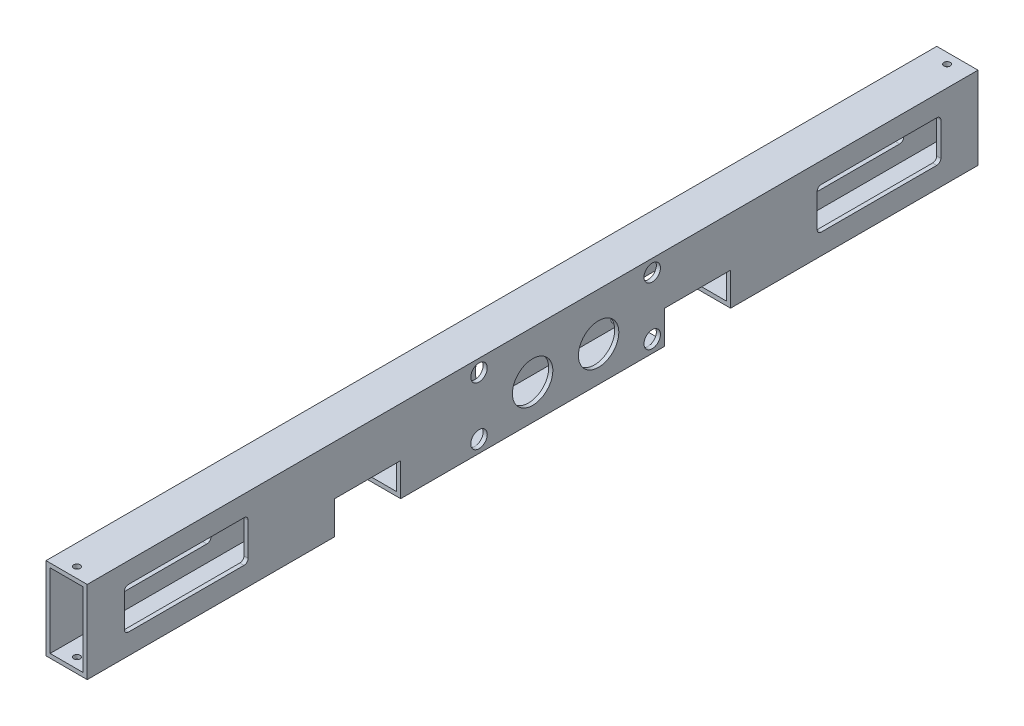
SolidWorks part; units mm, degrees
ref_plane "Front Plane" through (0, 0, 0) normal (0, 0, 1) x (1, 0, 0)
ref_plane "Top Plane" through (0, 0, 0) normal (0, 1, 0) x (1, 0, 0)
ref_plane "Right Plane" through (0, 0, 0) normal (1, 0, 0) x (0, 0, -1)
sketch "Sketch1" plane through (0, 0, 0) normal (0, 0, 1) x (1, 0, 0)
  line L1 (-12.1647, 2.5103) -> (19.5853, 2.5103)
  line L2 (-12.1647, 2.5103) -> (-12.1647, -60.9897)
  line L3 (-12.1647, -60.9897) -> (19.5853, -60.9897)
  line L4 (19.5853, 2.5103) -> (19.5853, -60.9897)
  line L5 (-8.9897, -0.6647) -> (16.4103, -0.6647)
  line L6 (-8.9897, -0.6647) -> (-8.9897, -57.8147)
  line L7 (-8.9897, -57.8147) -> (16.4103, -57.8147)
  line L8 (16.4103, -0.6647) -> (16.4103, -57.8147)
  dimension "D1" = 63.5
  dimension "D2" = 31.75
  dimension "D3" = 3.175
  dimension "D4" = 3.175
  dimension "D5" = 3.175
  dimension "D6" = 3.175
extrude "Boss-Extrude1" add sketch "Sketch1" along normal blind 685.8
sketch "Sketch3" plane through (-12.1647, 0, 0) normal (-1, 0, 0) x (0, 0, 1)
  line L0 (0, 2.5103) -> (0, -60.9897) construction
  line L1 (31.7754, -13.3647) -> (120.6754, -13.3647)
  line L2 (28.6004, -16.5397) -> (28.6004, -41.9397)
  line L3 (31.7754, -45.1147) -> (120.6754, -45.1147)
  line L4 (123.8504, -16.5397) -> (123.8504, -41.9397)
  line L5 (685.8, 2.5103) -> (0, 2.5103) construction
  line L6 (685.8, -60.9897) -> (0, -60.9897) construction
  line L7 (342.9, 2.5103) -> (342.9, -60.9897)
  line L8 (561.9496, -16.5397) -> (561.9496, -41.9397)
  line L9 (654.0246, -45.1147) -> (565.1246, -45.1147)
  line L10 (657.1996, -16.5397) -> (657.1996, -41.9397)
  line L11 (654.0246, -13.3647) -> (565.1246, -13.3647)
  line L12 (685.8, 2.5103) -> (685.8, -60.9897) construction
  line L13 (190.5, -60.9897) -> (241.3, -60.9897)
  line L14 (190.5, -60.9897) -> (190.5, -35.5897)
  line L15 (190.5, -35.5897) -> (241.3, -35.5897)
  line L16 (241.3, -60.9897) -> (241.3, -35.5897)
  line L17 (444.5, -60.9897) -> (495.3, -60.9897)
  line L18 (495.3, -60.9897) -> (495.3, -35.5897)
  line L19 (495.3, -35.5897) -> (444.5, -35.5897)
  line L20 (444.5, -60.9897) -> (444.5, -35.5897)
  arc A0 (28.6004, -41.9397) -> (31.7754, -45.1147) centre (31.7754, -41.9397) ccw
  arc A1 (120.6754, -45.1147) -> (123.8504, -41.9397) centre (120.6754, -41.9397) ccw
  arc A2 (120.6754, -13.3647) -> (123.8504, -16.5397) centre (120.6754, -16.5397) cw
  arc A3 (31.7754, -13.3647) -> (28.6004, -16.5397) centre (31.7754, -16.5397) ccw
  arc A4 (654.0246, -13.3647) -> (657.1996, -16.5397) centre (654.0246, -16.5397) cw
  arc A5 (565.1246, -13.3647) -> (561.9496, -16.5397) centre (565.1246, -16.5397) ccw
  arc A6 (565.1246, -45.1147) -> (561.9496, -41.9397) centre (565.1246, -41.9397) cw
  arc A7 (657.1996, -41.9397) -> (654.0246, -45.1147) centre (654.0246, -41.9397) cw
  line M7 (0, -60.9897) -> (685.8, -60.9897)
  dimension "D5" = 3.175
  dimension "D1" = 28.6004
  dimension "D2" = 15.875
  dimension "D3" = 15.875
  dimension "D4" = 95.25
  dimension "D6" = 25.4
  dimension "D7" = 50.8
  dimension "D8" = 190.5
  dimension "D9" = 50.8
  dimension "D10" = 25.4
  dimension "D11" = 190.5
extrude "Cut-Extrude1" cut sketch "Sketch3" against normal up to surface (31.75 mm away) contours L1 A3 L2 A0 L3 A1 L4 A2 | A7 L10 A4 L11 A5 L8 A6 L9 | L16 L15 L14 M7 | L20 L18 L19 M7 region at (-12.1647, -29.2397, 76.2254) region at (-12.1647, -29.2397, 609.5746) region at (-12.1647, -48.2897, 215.9) region at (-12.1647, -48.2897, 469.9) up to face at (19.5853, -29.2397, 342.9)
sketch "Sketch4" plane through (0, 2.5103, 0) normal (0, 1, 0) x (1, 0, 0)
  line L0 (19.5853, -685.8) -> (-12.1647, -685.8) construction
  line L1 (19.5853, 0) -> (-12.1647, 0) construction
  point P0 (3.7103, -677.8625)
  point P3 (3.7103, -685.8)
  point P4 (3.7103, -7.9375)
  dimension "D1" = 7.9375
  dimension "D2" = 7.9375
hole_wizard "#10 (0.1935) Diameter Hole1" positions "3DSketch1" profile "Sketch5" hole size "#10" standard "ANSI Inch" end condition through all
sketch3d "3DSketch1"
  point P0 (3.7103, 2.5103, 677.8625)
  point P3 (3.7103, 2.5103, 7.9375)
sketch "Sketch5" plane through (3.7103, 2.5103, 677.8625) normal (1, 0, 0) x (0, 0, 1)
  line L0 (0, 0) -> (0, 63.5)
  line L1 (0, 63.5) -> (2.4574, 63.5)
  line L2 (2.4574, 63.5) -> (2.4574, 0)
  line L5 (2.4574, 0) -> (0, 0)
  line L11 (0, -6.35) -> (0, 107.95) construction
  dimension "Thru Hole Dia." = 4.9149
  dimension "Thru Hole Depth" = 63.5
sketch "Sketch6" plane through (19.5853, 0, 0) normal (1, 0, 0) x (0, 0, -1)
  line L1 (-444.5, -60.9897) -> (-241.3, -60.9897) construction
  line L2 (-384.175, -7.0147) -> (-250.825, -7.0147) construction
  line L3 (-384.175, -7.0147) -> (-384.175, -51.4647) construction
  line L4 (-685.8, -60.9897) -> (-685.8, 2.5103) construction
  line L5 (-384.175, -51.4647) -> (-250.825, -51.4647) construction
  line L6 (-250.825, -7.0147) -> (-250.825, -51.4647) construction
  circle A0 centre (-342.9, -34.0022) radius 15.5575
  circle A1 centre (-292.1, -34.0022) radius 15.5575
  circle A2 centre (-384.175, -7.0147) radius 3.175
  circle A3 centre (-250.825, -7.0147) radius 3.175
  circle A4 centre (-384.175, -51.4647) radius 3.175
  circle A5 centre (-250.825, -51.4647) radius 3.175
  dimension "D1" = 31.115
  dimension "D4" = 50.8
  dimension "D6" = 17.4625
  dimension "D8" = 41.275
  dimension "D7" = 6.35
  dimension "D2" = 26.9875
  dimension "D3" = 342.9
  dimension "D5" = 26.9875
  dimension "D9" = 92.075
extrude "Cut-Extrude2" cut sketch "Sketch6" against normal up to surface (31.75 mm away) up to face at (-12.1647, -41.9397, 342.9)
sketch "Sketch7" plane through (19.5853, 0, 0) normal (1, 0, 0) x (0, 0, -1)
  circle A0 centre (-384.175, -7.0147) radius 6.35
  circle A1 centre (-384.175, -51.4647) radius 6.35
  circle A2 centre (-250.825, -51.4647) radius 6.35
  circle A3 centre (-250.825, -7.0147) radius 6.35
  dimension "D1" = 12.7
extrude "Cut-Extrude3" cut sketch "Sketch7" against normal up to next
